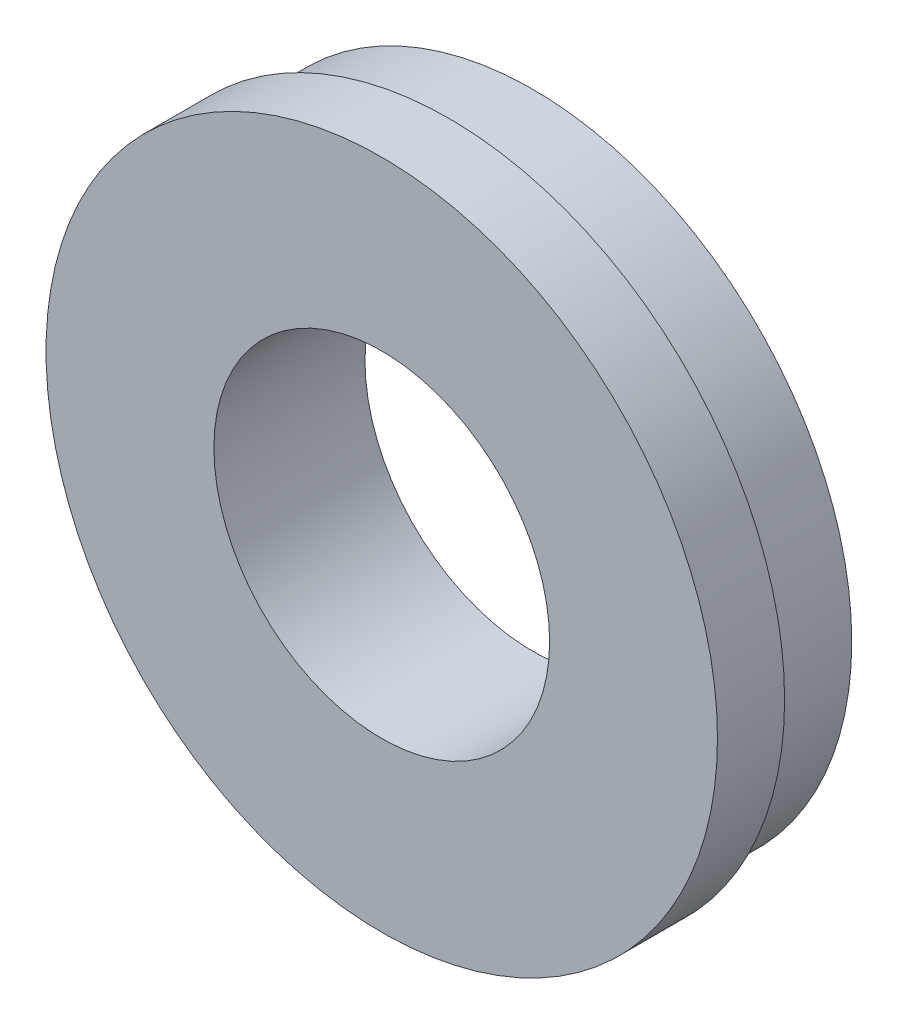
SolidWorks part; units mm, degrees
ref_plane "前视基准面" through (0, 0, 0) normal (0, 0, 1) x (1, 0, 0)
ref_plane "上视基准面" through (0, 0, 0) normal (0, 1, 0) x (1, 0, 0)
ref_plane "右视基准面" through (0, 0, 0) normal (1, 0, 0) x (0, 0, -1)
ref_plane "基准面4" through (0, 0, 0) normal (1, 0, 0) x (0, 0, -1)
sketch "草图1" plane through (0, 0, 0) normal (1, 0, 0) x (0, 0, -1)
  line L0 (0, 0) -> (0, 4)
  line L1 (0, 4) -> (0.8, 4)
  line L2 (0.8, 4) -> (0.8, 3.8)
  line L3 (0.8, 3.8) -> (1.8, 3.8)
  line L4 (1.8, 3.8) -> (1.8, 0)
  line L5 (1.8, 0) -> (0, 0)
  line L6 (1.8, 0) -> (0, 0) construction
revolve "旋转1" add sketch "草图1" angle 360 about L6 reverse direction yes
sketch "草图2" plane through (0, 0, 0) normal (1, 0, 0) x (0, 0, -1)
  line L0 (0, 0) -> (0, 2)
  line L1 (0, 2) -> (1.8, 2)
  line L2 (1.8, 2) -> (1.8, 0)
  line L3 (1.8, 0) -> (0, 0)
  line L4 (1.8, 0) -> (0, 0) construction
revolve "切除-旋转1" cut sketch "草图2" angle 360 about L4 reverse direction yes
ref_plane "基准面5" through (0, 0, 0) normal (0, 0, 1) x (1, 0, 0)
ref_plane "to_motor XY" through (0, 0, 0) normal (0, 0, 1) x (1, 0, 0)
ref_plane "to_motor XZ" through (0, 0, 0) normal (0, -1, 0) x (-1, 0, 0)
ref_plane "to_motor YZ" through (0, 0, 0) normal (1, 0, 0) x (0, 0, -1)
ref_axis "to_motor X" through (-80.9, 0, 0) along (1, 0, 0)
ref_axis "to_motor Y" through (0, -50, 0) along (0, 1, 0)
ref_axis "to_motor Z" through (0, 0, 80.9) along (0, 0, -1)
sketch3d "to_motor"
  point P0 (0, 0, 0)
